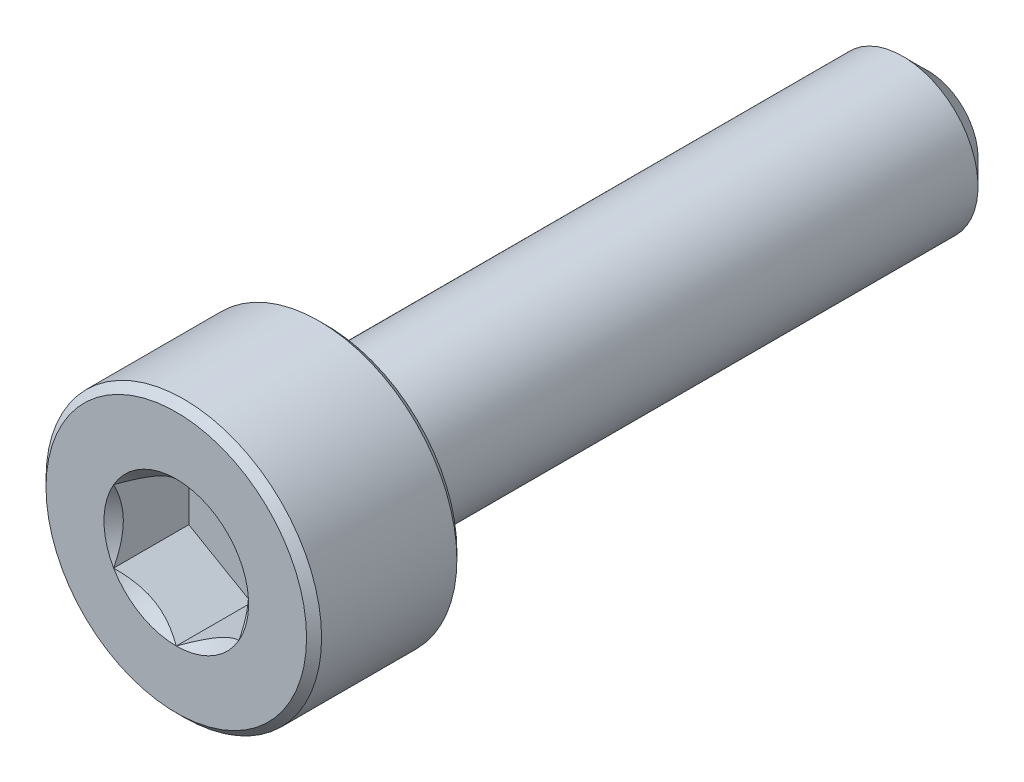
SolidWorks part; units mm, degrees
ref_plane "Front Plane" through (0, 0, 0) normal (0, 0, 1) x (1, 0, 0)
ref_plane "Top Plane" through (0, 0, 0) normal (0, 1, 0) x (1, 0, 0)
ref_plane "Right Plane" through (0, 0, 0) normal (1, 0, 0) x (0, 0, -1)
sketch "Sketch1" plane through (0, 0, 0) normal (1, 0, 0) x (0, 0, -1)
  line L0 (-7.5, 0) -> (7.5, 0) construction
  line L1 (7.5, 0) -> (7.5, 1) construction
  line L2 (7.5, 1) -> (7, 1.5) construction
  line L3 (7, 1.5) -> (-4.5, 1.5) construction
  line L5 (-4.5, 1.5) -> (-4.5, 2.75) construction
  line L6 (-4.5, 2.75) -> (-7.5, 2.75) construction
  line L7 (-7.5, 2.75) -> (-7.5, 0) construction
  line L8 (7.5, 1) -> (7.5, 1.5) construction
  line L9 (7.4688, 1.5541) -> (7.7188, 1.1211) construction
  line L10 (7.7188, 1.1211) -> (7.9688, 1.5541) construction
  line L11 (7.9688, 1.5541) -> (7.4688, 1.5541) construction
  line L12 (7.7188, 1.5541) -> (7.7188, 1.5) construction
  line L13 (7.7188, 1.1211) -> (7.7188, 1.1752) construction
  line L14 (7.6875, 1.1752) -> (7.75, 1.1752) construction
  line L15 (7.5, 1.5) -> (7.9375, 1.5) construction
  line L16 (7.4844, 1.5271) -> (7.9531, 1.5271) construction
  line L17 (7.5, 0) -> (7.5, -1.5) construction
  line L18 (-4.65, 2.75) -> (-4.5, 2.6) construction
  line L19 (-7.35, 2.75) -> (-7.5, 2.6) construction
  point P0 (-7.5, 1.25)
  point P3 (5.75, 1.5)
  point P4 (0, 0)
  point P22 (7.7188, 1.1752)
  point P24 (-4.5, 1.5)
  point P25 (7.7188, 1.5)
  point P28 (7.7188, 1.5271)
  point P29 (5.75, -1.5)
  point P31 (-6, 2.75)
  point P37 (-5.025, 2.75)
  point P38 (-7.275, 2.75)
  point P41 (-6, 0)
  dimension "head height" = 3
  dimension "D1" = 45
  dimension "Head Diameter" = 5.5
  dimension "Thread Size" = 3
  dimension "drive size" = 2.5
  dimension "Thread Pitch" = 0.5
  dimension "D2" = 0.0625
  dimension "D3" = 0.5
  dimension "D4" = 1.75
  dimension "D7" = 0.15
  dimension "D8" = 0.15
  dimension "D9" = 0.15
  dimension "D10" = 0.075
  dimension "D11" = 0.375
  dimension "length" = 12
  dimension "Drive Depth" = 1.5
sketch "Sketch2" plane through (0, 0, 0) normal (1, 0, 0) x (0, 0, -1)
  line L1 (-7.35, 2.75) -> (-4.65, 2.75)
  line L4 (7, 1.5) -> (7.5, 1)
  line L5 (7.5, 1) -> (7.5, 0)
  line L6 (-4.65, 2.75) -> (-4.5, 2.6) construction
  line L7 (7.5, 0) -> (-7.5, 0)
  line L8 (-7.35, 2.75) -> (-7.5, 2.6) construction
  line L9 (-4.65, 2.75) -> (-4.5, 2.6)
  line L10 (-7.35, 2.75) -> (-7.5, 2.6)
  line L11 (-7.5, 2.6) -> (-7.5, 0)
  line L12 (-4.5, 2.6) -> (-4.5, 1.5)
  line L13 (-4.5, 1.5) -> (7, 1.5)
revolve "Revolve1" add sketch "Sketch2" angle 360 about L7
sketch "Sketch3" plane through (0, 0, 7.5) normal (0, 0, 1) x (1, 0, 0)
  line L1 (0, 1.4434) -> (-1.25, 0.7217)
  line L2 (-1.25, 0.7217) -> (-1.25, -0.7217)
  line L3 (-1.25, -0.7217) -> (0, -1.4434)
  line L4 (0, -1.4434) -> (1.25, -0.7217)
  line L5 (1.25, -0.7217) -> (1.25, 0.7217)
  line L6 (1.25, 0.7217) -> (0, 1.4434)
  circle A0 centre (0, 0) radius 1.25 construction
  dimension "D1" = 2.5
extrude "Cut-Extrude1" cut sketch "Sketch3" against normal up to vertex (1.5 mm away) up to point (0, 0, 6)
sketch "Sketch4" plane through (0, 0, 7.5) normal (0, 0, 1) x (1, 0, 0)
  circle A0 centre (0, 0) radius 1.4434
extrude "Cut-Extrude2" cut sketch "Sketch4" against normal blind 0.5 draft 45
ref_plane "Plane1" [suppressed] through (0, 0, 4.5) normal (0, 0, 1) x (1, 0, 0)
split "Split1" [suppressed] bodies to split 106
sketch "Sketch6" [suppressed] plane through (0, 0, -7.5) normal (0, 0, -1) x (-1, 0, 0)
  circle A0 centre (0, 0) radius 1.5
curve "Helix/Spiral1" [suppressed] pitch 0.5 height 12.5 turns 25
sketch "Sketch7" [suppressed] plane through (0, 0, 0) normal (1, 0, 0) x (0, 0, -1)
  line L0 (7.4844, 1.5271) -> (7.9531, 1.5271)
  line L1 (7.9531, 1.5271) -> (7.75, 1.1752)
  line L2 (7.75, 1.1752) -> (7.6875, 1.1752)
  line L3 (7.6875, 1.1752) -> (7.4844, 1.5271)
sweep "Cut-Sweep1" [suppressed] cut profiles "Sketch7" path "Helix/Spiral1"
sketch "Sketch8" [suppressed] plane through (0, 0, 4.5) normal (0, 0, -1) x (-1, 0, 0)
  circle A0 centre (0, 0) radius 1.5
extrude "Boss-Extrude1" [suppressed] add sketch "Sketch8" along normal through all draft 45
ref_plane "Plane2" [suppressed] through (0, 0, 6) normal (0, 0, 1) x (1, 0, 0)
sketch "Sketch9" [suppressed] plane through (0, 0, 6) normal (0, 0, 1) x (1, 0, 0)
  line L0 (0, 2.6744) -> (0.072, 2.7491)
  line L1 (0, 2.6744) -> (-0.072, 2.7491)
  line L2 (0, 2.75) -> (0, 0) construction
  line L3 (-0.072, 2.7491) -> (0, 0) construction
  line L4 (0, 0) -> (0.072, 2.7491) construction
  arc A0 (0.072, 2.7491) -> (-0.072, 2.7491) centre (0, 0) ccw
  circle A1 centre (0, 0) radius 2.6744 construction
  dimension "D1" = 5.5
  dimension "D2" = 5.3487
  dimension "D3" = 3
extrude "Cut-Extrude4" [suppressed] cut sketch "Sketch9" against normal up to vertex and the other way up to vertex
pattern_circular "CirPattern2" [suppressed] count 96 over 360 about axis through (0, 0, 7.5) along (0, 0, -1) of bodies 113
equation "\"D2@Sketch1\" = \"Thread Pitch@Sketch1\" / 8"
equation "\"D3@Sketch1\" = \"Thread Pitch@Sketch1\""
equation "\"D3@Helix/Spiral1\" = \"length@Sketch1\" + \"Thread Pitch@Sketch1\""
equation "\"D4@Helix/Spiral1\" = \"Thread Pitch@Sketch1\""
equation "\"D4@Sketch1\" = \"Thread Pitch@Sketch1\" * 3.5"
equation "\"D7@Sketch1\"=\"head height@Sketch1\"*.05"
equation "\"D8@Sketch1\"=\"D7@Sketch1\""
equation "\"D9@Sketch1\"=\"D7@Sketch1\""
equation "\"D10@Sketch1\"=\"D7@Sketch1\"/2"
equation "\"D11@Sketch1\"=\"D10@Sketch1\"*5"
equation "\"D1@CirPattern2\"=( 360 / \"D3@Sketch9\" )*0.8"
equation "\"D1@Sketch3\" = \"drive size@Sketch1\""
equation "\"D2@Sketch9\"=\"Head Diameter@Sketch1\" * 0.9725"
